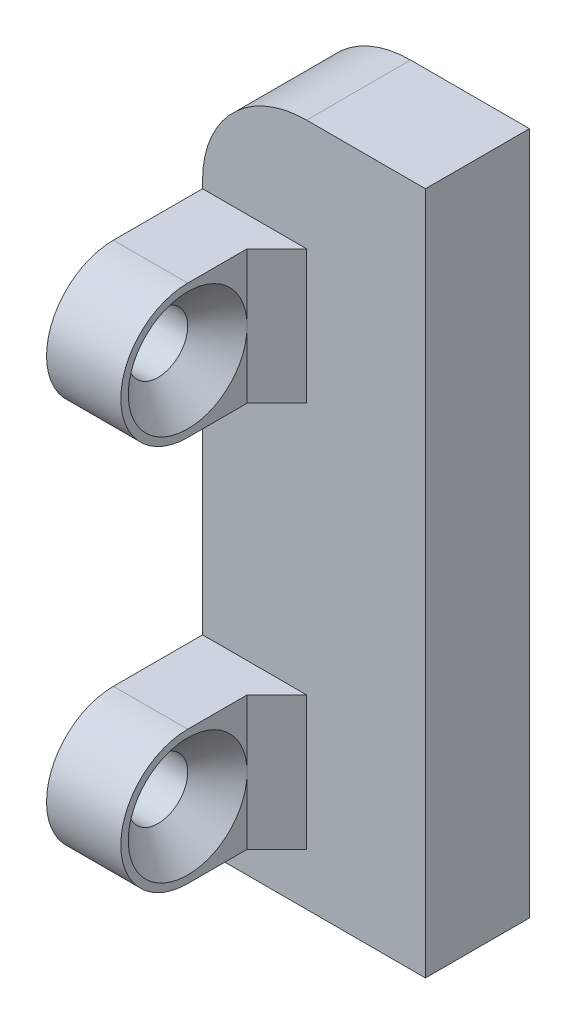
SolidWorks part; units mm, degrees
ref_plane "Front Plane" through (0, 0, 0) normal (0, 0, 1) x (1, 0, 0)
ref_plane "Top Plane" through (0, 0, 0) normal (0, 1, 0) x (1, 0, 0)
ref_plane "Right Plane" through (0, 0, 0) normal (1, 0, 0) x (0, 0, -1)
sketch "Sketch1" plane through (0, 0, 0) normal (0, 0, 1) x (1, 0, 0)
  line L0 (22, 21) -> (14, 21)
  line L1 (7, 14) -> (7, -25)
  line L2 (7, -25) -> (22, -25)
  line L3 (22, -25) -> (22, 21)
  arc A0 (14, 21) -> (7, 14) centre (14, 14) ccw
extrude "Boss-Extrude1" add sketch "Sketch1" along normal blind 7
sketch "Sketch2" plane through (7, 0, 0) normal (-1, 0, 0) x (0, 0, 1)
  line L0 (7, 13.5) -> (13, 13.5)
  line L1 (7, 14) -> (7, -25) construction
  line L3 (7, 4.5) -> (13, 4.5)
  line L4 (7, 13.5) -> (7, 4.5)
  line L9 (13, 9) -> (15, 9) construction
  arc A0 (13, 13.5) -> (13, 4.5) centre (13, 9) cw
  arc A3 (15, 7) -> (15, 11) centre (15, 9) ccw construction
  circle A4 centre (13, 9) radius 2
  dimension "D3" = 4
  dimension "D1" = 9
  dimension "D2" = 6
extrude "Boss-Extrude2" add sketch "Sketch2" against normal blind 5
ref_plane "Plane1" through (0, -4, 0) normal (0, 1, 0) x (1, 0, 0)
mirror "Mirror1" about plane through (0, -4, 0) normal (0, 1, 0) of "Boss-Extrude2"
chamfer "Chamfer1" distance 2 angle 45 2 edges at (12, -15, 13) (12, 7, 13)
chamfer "Chamfer2" distance 2 angle 45 2 edges at (12, -17, 7) (12, 9, 7)
